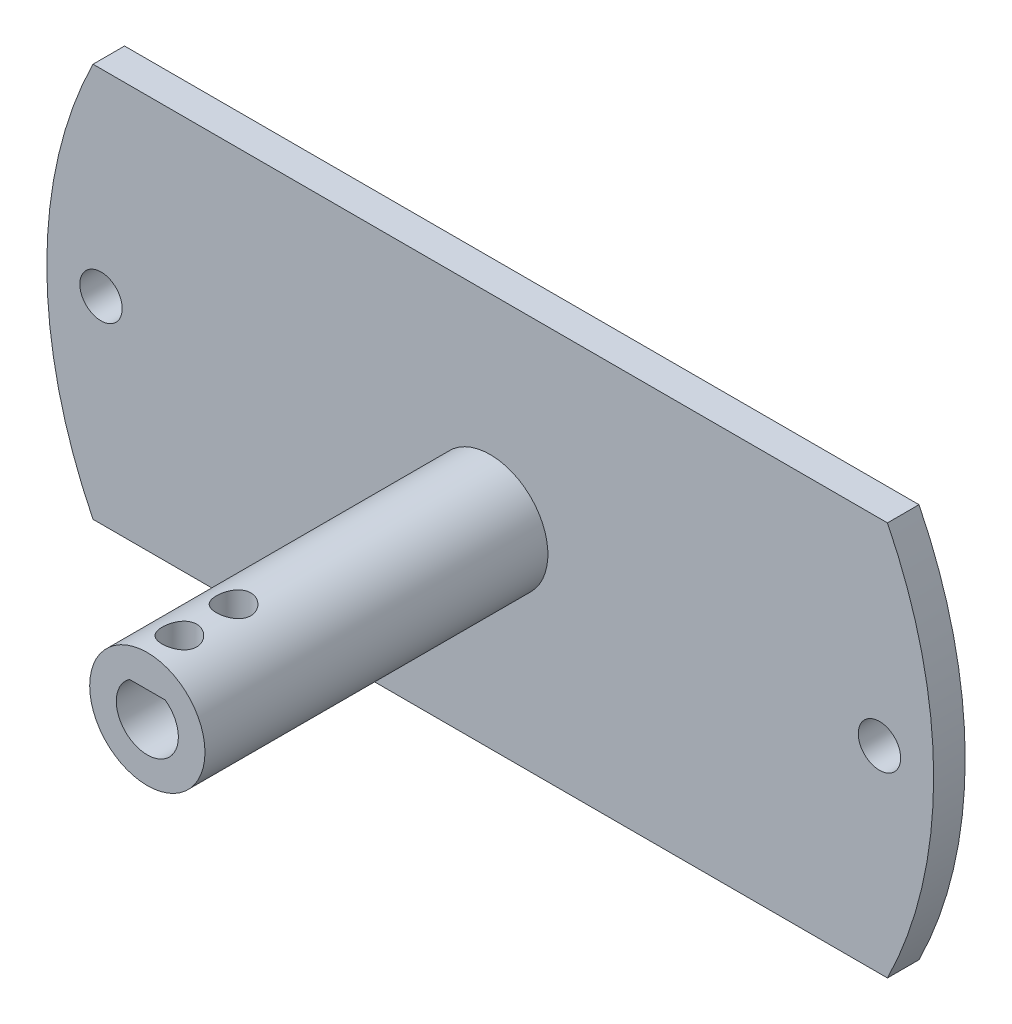
SolidWorks part; units mm, degrees
ref_plane "Alzado" through (0, 0, 0) normal (0, 0, 1) x (1, 0, 0)
ref_plane "Planta" through (0, 0, 0) normal (0, 1, 0) x (1, 0, 0)
ref_plane "Vista lateral" through (0, 0, 0) normal (1, 0, 0) x (0, 0, -1)
sketch "Croquis1" plane through (0, 0, 0) normal (0, 0, 1) x (1, 0, 0)
  line L0 (0, 0) -> (0, 2.5851) construction
  line L7 (-1.8, 2.5851) -> (1.8, 2.5851)
  circle A0 centre (0, 0) radius 5.85
  arc A1 (-1.8, 2.5851) -> (1.8, 2.5851) centre (0, 0) ccw
  point P14 (0, 2.5851)
  dimension "D2" = 6.3
  dimension "D1" = 11.7
  dimension "D3" = 3.6
extrude "Saliente-Extruir1" add sketch "Croquis1" along normal blind 38
sketch "Croquis2" plane through (0, 2.5851, 0) normal (0, 1, 0) x (1, 0, 0)
  line L0 (0, -38) -> (0, -34.75) construction
  line L2 (0, -34.75) -> (0, -33) construction
  line L3 (0, -33) -> (0, -31) construction
  line L4 (0, -31) -> (0, -29.25) construction
  line L5 (0, -29.25) -> (0, -26) construction
  line L6 (-5.85, -38) -> (5.85, -38) construction
  circle A0 centre (0, -34.75) radius 1.75
  circle A1 centre (0, -29.25) radius 1.75
  dimension "D1" = 3.5
  dimension "D2" = 12
  dimension "D3" = 2
extrude "Cortar-Extruir1" cut sketch "Croquis2" along normal blind 7.5
sketch "Croquis3" plane through (0, 0, 0) normal (0, 0, -1) x (-1, 0, 0)
  circle A0 centre (0, 0) radius 45
  dimension "D1" = 90
extrude "Saliente-Extruir2" add sketch "Croquis3" against normal blind 3.2
sketch "Croquis5" plane through (0, 0, 0) normal (0, 0, -1) x (-1, 0, 0)
  line L0 (0, 0) -> (0, 7.5) construction
  line L1 (0, 7.5) -> (-7.5, 7.5) construction
  line L2 (0, 0) -> (-34, 0) construction
  line L3 (-34, 0) -> (-45, 0) construction
  line L4 (0, 7.5) -> (0, 20) construction
  line L5 (0, 20) -> (-75, 20)
  line L6 (-75, 20) -> (-75, 50)
  line L7 (-75, 50) -> (75, 50)
  line L8 (75, 50) -> (75, 20)
  line L9 (75, 20) -> (0, 20)
  line L10 (75, -50) -> (75, -20)
  line L11 (-75, -50) -> (75, -50)
  line L12 (-75, -20) -> (-75, -50)
  line L13 (0, -20) -> (-75, -20)
  line L14 (75, -20) -> (0, -20)
  circle A4 centre (0, 0) radius 45 construction
  circle A5 centre (-39.5, 0) radius 2.15
  circle A6 centre (39.5, 0) radius 2.15
  point P14 (0.2713, -0.2713)
  dimension "D3" = 45
  dimension "D5" = 4.3
  dimension "D1" = 7.5
  dimension "D2" = 7.5
  dimension "D4" = 34
  dimension "D6" = 20
  dimension "D7" = 30
  dimension "D8" = 150
extrude "Cortar-Extruir2" cut sketch "Croquis5" against normal blind 5 and the other way through all
